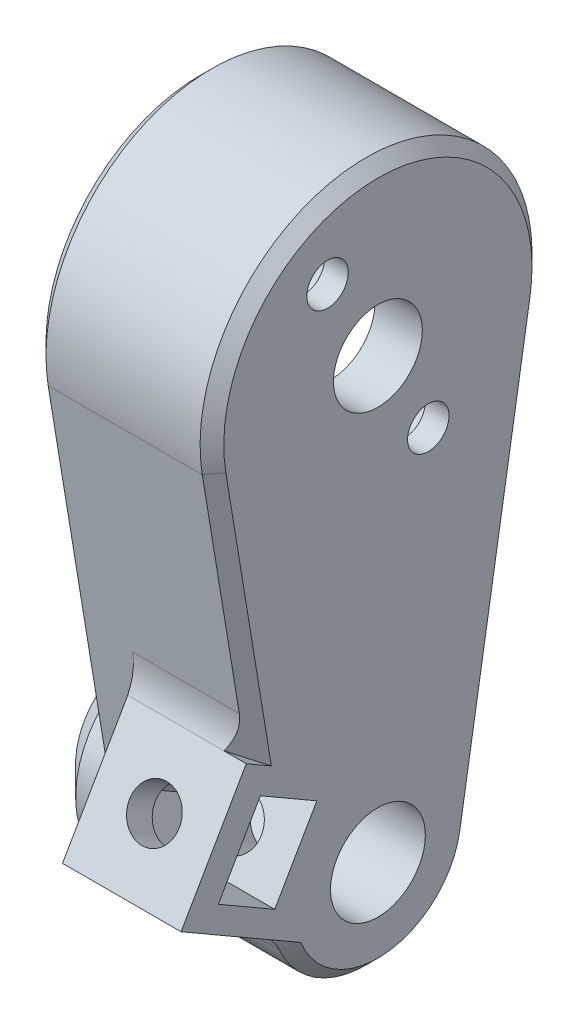
SolidWorks part; units mm, degrees
material "3D printed plastic"
ref_plane "Front Plane" through (0, 0, 0) normal (0, 0, 1) x (1, 0, 0)
ref_plane "Top Plane" through (0, 0, 0) normal (0, 1, 0) x (1, 0, 0)
ref_plane "Right Plane" through (0, 0, 0) normal (1, 0, 0) x (0, 0, -1)
sketch "Sketch1" plane through (0, 0, 0) normal (1, 0, 0) x (0, 0, -1)
  circle A0 centre (0, 0) radius 4
  circle A1 centre (0, 0) radius 8
  dimension "D1" = 8
  dimension "D2" = 16
extrude "Boss-Extrude1" add sketch "Sketch1" against normal blind 20
sketch "Sketch2" plane through (0, 0, 0) normal (1, 0, 0) x (0, 0, -1)
  line L0 (13.8147, 34.7297) -> (7.8941, -1.2973)
  line L1 (-7.8941, -1.2973) -> (-13.8147, 34.7297)
  line L2 (0, 37) -> (0, 0) construction
  line L3 (4.25, 29.6388) -> (-4.25, 44.3612) construction
  arc A0 (13.8147, 34.7297) -> (-13.8147, 34.7297) centre (0, 37) ccw
  circle A1 centre (0, 0) radius 8 construction
  arc A2 (7.8941, -1.2973) -> (-7.8941, -1.2973) centre (0, 0) ccw
  circle A3 centre (0, 37) radius 3.75
  circle A4 centre (-4.25, 44.3612) radius 1.75
  circle A5 centre (4.25, 29.6388) radius 1.75
  dimension "D1" = 28
  dimension "D3" = 7.5
  dimension "D4" = 3.5
  dimension "D2" = 37
  dimension "D5" = 17
  dimension "D6" = 30
extrude "Boss-Extrude2" add sketch "Sketch2" against normal blind 4
sketch "Sketch4" plane through (-4, 0, 0) normal (-1, 0, 0) x (0, 0, 1)
  circle A0 centre (4.25, 44.3612) radius 3.5
  circle A1 centre (-4.25, 29.6388) radius 3.5
  dimension "D1" = 7
extrude "Cut-Extrude1" cut sketch "Sketch4" against normal blind 2
sketch "Sketch5" plane through (-4, 0, 0) normal (-1, 0, 0) x (0, 0, 1)
  line L0 (13.8147, 34.7297) -> (7.8941, -1.2973)
  line L1 (9.8124, 41.2091) -> (4.1629, 6.8316)
  line L2 (-13.4884, 40.75) -> (-11.399, 40.75)
  arc A0 (7.8941, -1.2973) -> (4.1629, 6.8316) centre (0, 0) ccw
  circle A1 centre (0, 37) radius 3.75 construction
  arc A2 (13.8147, 34.7297) -> (-13.4884, 40.75) centre (0, 37) ccw
  arc A3 (8.3633, 45.6055) -> (-11.399, 40.75) centre (0, 37) ccw
  arc A4 (9.8124, 41.2091) -> (8.3633, 45.6055) centre (4.8786, 42.0199) ccw
  dimension "D1" = 2
  dimension "D2" = 5
  dimension "D3" = 5
extrude "Boss-Extrude3" add sketch "Sketch5" along normal blind 11
chamfer "Chamfer1" distance 1 angle 45 6 edges at (0, -8, 0) (0, 16.7162, -10.8544) (0, 16.7162, 10.8544) (0, 51, 0) (-15, 50.6716, 3.0146) (-15, 16.7162, 10.8544)
chamfer "Chamfer2" distance 2.5 angle 45 1 edges at (-20, 0, -8)
sketch "Sketch6" plane through (0, 0, 0) normal (1, 0, 0) x (0, 0, -1)
  line L0 (-6.2141, -2.7631) -> (-0.7141, 6.7631)
  line L1 (-6.2141, -2.7631) -> (-16.6064, 3.2369)
  line L2 (-0.7141, 6.7631) -> (-11.1064, 12.7631)
  line L3 (-16.6064, 3.2369) -> (-11.1064, 12.7631)
  line L4 (-13.8564, 8) -> (0, 0) construction
  line L5 (0, 0) -> (0, 2.6754) construction
  circle A0 centre (0, 0) radius 4 construction
  dimension "D1" = 11
  dimension "D2" = 12
  dimension "D3" = 60
extrude "Boss-Extrude4" add sketch "Sketch6" against normal blind 10
fillet "Fillet1" radius 5 2 edges at (-5.5, -1.8584, 7.7812) (-5.5, 12.188, 10.1103)
sketch "Sketch7" plane through (0, 8, 13.8564) normal (0, 0.5, 0.866) x (1, 0, 0)
  line L0 (0, 0) -> (-5, 0) construction
  circle A0 centre (-5, 0) radius 2.1
  dimension "D1" = 4.2
  dimension "D2" = 5
extrude "Cut-Extrude2" cut sketch "Sketch7" against normal up to next
sketch "Sketch8" plane through (0, 8, 13.8564) normal (0, 0.5, 0.866) x (1, 0, 0)
  line L0 (-2.9504, 3.55) -> (0, 3.55)
  line L1 (-0.9008, 0) -> (-2.9504, 3.55) construction
  line L2 (-2.9504, 3.55) -> (-7.0496, 3.55)
  line L3 (-7.0496, 3.55) -> (-9.0992, 0)
  line L4 (-9.0992, 0) -> (-7.0496, -3.55)
  line L5 (-7.0496, -3.55) -> (-2.9504, -3.55)
  line L6 (-2.9504, -3.55) -> (-0.9008, 0) construction
  line L7 (0, 5.5) -> (0, -5.5) construction
  line L8 (0, 3.55) -> (0, -3.55)
  line L9 (0, -3.55) -> (-2.9504, -3.55)
  circle A0 centre (-5, 0) radius 3.55 construction
  dimension "D1" = 7.1
extrude "Cut-Extrude3" cut sketch "Sketch8" against normal blind 5.5 from offset 2.5
